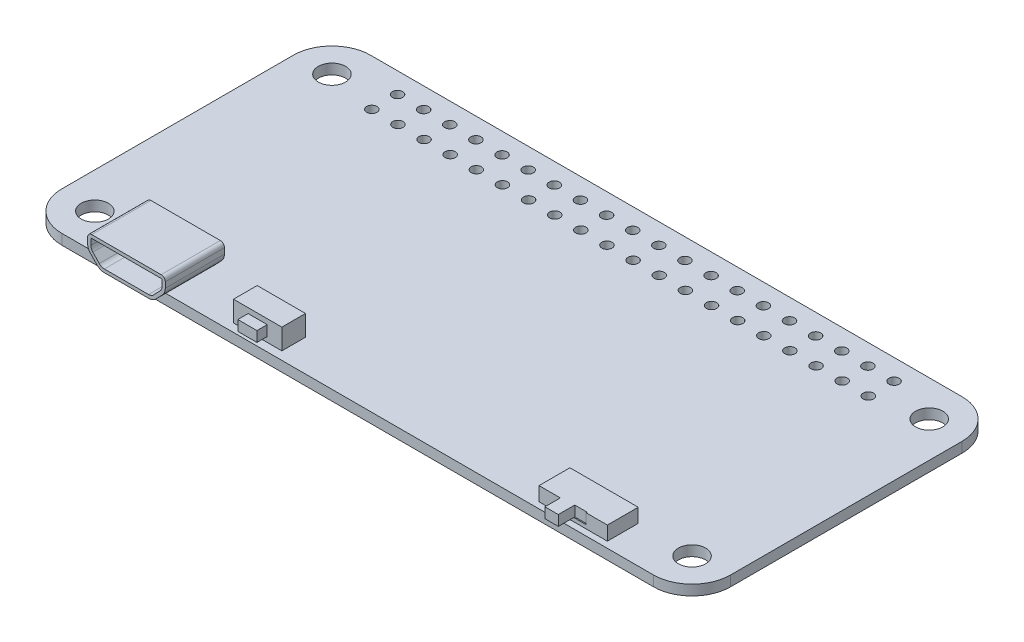
SolidWorks part; units mm, degrees
ref_plane "Front Plane" through (0, 0, 0) normal (0, 0, 1) x (1, 0, 0)
ref_plane "Top Plane" through (0, 0, 0) normal (0, 1, 0) x (1, 0, 0)
ref_plane "Right Plane" through (0, 0, 0) normal (1, 0, 0) x (0, 0, -1)
sketch "Sketch1" plane through (0, 0, 0) normal (0, 1, 0) x (1, 0, 0)
  line L1 (-28.75, 15) -> (28.75, 15)
  line L2 (-32.5, 11.25) -> (-32.5, -11.25)
  line L3 (-28.75, -15) -> (28.75, -15)
  line L4 (32.5, 11.25) -> (32.5, -11.25)
  line L5 (-32.5, 15) -> (32.5, -15) construction
  line L6 (-32.5, -15) -> (32.5, 15) construction
  arc A0 (-32.5, -11.25) -> (-28.75, -15) centre (-28.75, -11.25) ccw
  arc A1 (28.75, -15) -> (32.5, -11.25) centre (28.75, -11.25) ccw
  arc A2 (28.75, 15) -> (32.5, 11.25) centre (28.75, 11.25) cw
  arc A3 (-28.75, 15) -> (-32.5, 11.25) centre (-28.75, 11.25) ccw
  point P0 (0, 0)
  dimension "D3" = 3.75
  dimension "D1" = 65
  dimension "D2" = 30
extrude "Boss-Extrude1" add sketch "Sketch1" along normal blind 1 contours L1 A2 L4 A1 L3 A0 L2 A3
sketch "Sketch2" plane through (0, 1, 0) normal (0, 1, 0) x (1, 0, 0)
  line L0 (0, 15) -> (0, -15) construction
  line L1 (-28.75, 15) -> (28.75, 15) construction
  line L2 (-28.75, -15) -> (28.75, -15) construction
  line L3 (-32.5, 0) -> (32.5, 0) construction
  line L4 (-32.5, 11.25) -> (-32.5, -11.25) construction
  line L5 (32.5, 11.25) -> (32.5, -11.25) construction
  circle A0 centre (-29.025, 11.525) radius 1.325
  circle A2 centre (29.025, 11.525) radius 1.325
  circle A3 centre (29.025, -11.525) radius 1.325
  circle A4 centre (-29.025, -11.525) radius 1.325
  dimension "D1" = 2.65
  dimension "D2" = 2.15
  dimension "D3" = 2.15
extrude "Cut-Extrude1" cut sketch "Sketch2" against normal through all
sketch "Sketch3" plane through (0, 1, 0) normal (0, 1, 0) x (1, 0, 0)
  line L0 (-24.128, 13) -> (-24.128, 10.5) construction
  line L3 (-28.75, 15) -> (28.75, 15) construction
  line L5 (-32.5, 11.25) -> (-32.5, -11.25) construction
  circle A0 centre (-24.128, 13) radius 0.5
  circle A1 centre (-24.128, 10.5) radius 0.5
  dimension "D1" = 1
  dimension "D3" = 1.5
  dimension "D4" = 7.872
  dimension "D2" = 2.5
extrude "Cut-Extrude2" cut sketch "Sketch3" against normal through all
pattern_linear "LPattern1" count 20 spacing 2.54 along (1, 0, 0) of "Cut-Extrude2"
sketch "Sketch15" plane through (0, 0, 15) normal (0, 0, 1) x (1, 0, 0)
  line L0 (-21.225, 1) -> (-21.225, 3.6) construction
  line L1 (-28.75, 1) -> (28.75, 1) construction
  line L2 (-24.6, 3.6) -> (-17.85, 3.6)
  line L3 (-17.45, 3.2) -> (-17.45, 2.6523)
  line L4 (-17.7286, 1.9598) -> (-18.3548, 1.3075)
  line L5 (-19.0762, 1) -> (-23.3738, 1)
  line L7 (-24.7214, 1.9598) -> (-24.0952, 1.3075)
  line L8 (-25, 3.2) -> (-25, 2.6523)
  line L9 (15.325, 0) -> (15.325, 5.5788) construction
  line L10 (-28.75, 0) -> (28.75, 0) construction
  line L11 (-32.5, 1) -> (-32.5, 0) construction
  arc A0 (-18.3548, 1.3075) -> (-19.0762, 1) centre (-19.0762, 2) cw
  arc A1 (-24.0952, 1.3075) -> (-23.3738, 1) centre (-23.3738, 2) ccw
  arc A2 (-17.45, 2.6523) -> (-17.7286, 1.9598) centre (-18.45, 2.6523) cw
  arc A3 (-24.7214, 1.9598) -> (-25, 2.6523) centre (-24, 2.6523) cw
  arc A4 (-17.85, 3.6) -> (-17.45, 3.2) centre (-17.85, 3.2) cw
  arc A5 (-25, 3.2) -> (-24.6, 3.6) centre (-24.6, 3.2) cw
  point P14 (-18.65, 1)
  point P17 (-23.8, 1)
  point P20 (-17.45, 2.25)
  point P23 (-25, 2.25)
  point P26 (-17.45, 3.6)
  point P29 (-25, 3.6)
  dimension "D6" = 1
  dimension "D7" = 0.4
  dimension "D1" = 7.55
  dimension "D2" = 2.6
  dimension "D3" = 1.35
  dimension "D4" = 5.15
  dimension "D5" = 7.5
extrude "Boss-Extrude6" add sketch "Sketch15" along normal blind 1.25 and the other way blind 4.5
sketch "Sketch16" plane through (0, 0, 16.25) normal (0, 0, 1) x (1, 0, 0)
  line L30 (-18.5857, 1.5291) -> (-17.9595, 2.1814)
  line L31 (-17.77, 2.6523) -> (-17.77, 3.2)
  line L32 (-17.85, 3.28) -> (-24.6, 3.28)
  line L33 (-24.68, 3.2) -> (-24.68, 2.6523)
  line L34 (-24.4905, 2.1814) -> (-23.8643, 1.5291)
  line L35 (-23.3738, 1.32) -> (-19.0762, 1.32)
  line L36 (-18.5857, 1.5291) -> (-17.9595, 2.1814)
  line L37 (-17.77, 2.6523) -> (-17.77, 3.2)
  line L38 (-17.85, 3.28) -> (-24.6, 3.28)
  line L39 (-24.68, 3.2) -> (-24.68, 2.6523)
  line L40 (-24.4905, 2.1814) -> (-23.8643, 1.5291)
  line L41 (-23.3738, 1.32) -> (-19.0762, 1.32)
  arc A30 (-19.0762, 1.32) -> (-18.5857, 1.5291) centre (-19.0762, 2) ccw
  arc A31 (-17.9595, 2.1814) -> (-17.77, 2.6523) centre (-18.45, 2.6523) ccw
  arc A32 (-17.77, 3.2) -> (-17.85, 3.28) centre (-17.85, 3.2) ccw
  arc A33 (-24.6, 3.28) -> (-24.68, 3.2) centre (-24.6, 3.2) ccw
  arc A34 (-24.68, 2.6523) -> (-24.4905, 2.1814) centre (-24, 2.6523) ccw
  arc A35 (-23.8643, 1.5291) -> (-23.3738, 1.32) centre (-23.3738, 2) ccw
  arc A36 (-19.0762, 1.32) -> (-18.5857, 1.5291) centre (-19.0762, 2) ccw
  arc A37 (-17.9595, 2.1814) -> (-17.77, 2.6523) centre (-18.45, 2.6523) ccw
  arc A38 (-17.77, 3.2) -> (-17.85, 3.28) centre (-17.85, 3.2) ccw
  arc A39 (-24.6, 3.28) -> (-24.68, 3.2) centre (-24.6, 3.2) ccw
  arc A40 (-24.68, 2.6523) -> (-24.4905, 2.1814) centre (-24, 2.6523) ccw
  arc A41 (-23.8643, 1.5291) -> (-23.3738, 1.32) centre (-23.3738, 2) ccw
  dimension "D2" = 0.32
extrude "Cut-Extrude9" cut sketch "Sketch16" against normal blind 5.25
sketch "草图1" plane through (0, 1, 0) normal (0, 1, 0) x (1, 0, 0)
  line L0 (-32.5, 11.25) -> (-32.5, -11.25) construction
  line L1 (-12.87, -11.9) -> (-8.17, -11.9)
  line L2 (-12.87, -11.9) -> (-12.87, -14.2)
  line L3 (-12.87, -14.2) -> (-8.17, -14.2)
  line L4 (-8.17, -11.9) -> (-8.17, -14.2)
  line L5 (-28.75, -15) -> (-23.3738, -15) construction
  dimension "D1" = 4.7
  dimension "D2" = 2.3
  dimension "D3" = 19.63
  dimension "D4" = 0.8
extrude "凸台-拉伸1" add sketch "草图1" along normal blind 2
sketch "草图2" plane through (0, 0, 14.2) normal (0, 0, 1) x (1, 0, 0)
  line L0 (-12.87, 3) -> (-8.17, 3) construction
  line L5 (-11.45, 2.5) -> (-9.59, 2.5)
  line L6 (-11.45, 2.5) -> (-11.45, 1.5)
  line L7 (-11.45, 1.5) -> (-9.59, 1.5)
  line L8 (-9.59, 2.5) -> (-9.59, 1.5)
  line L9 (-11.45, 2.5) -> (-9.59, 1.5) construction
  line L10 (-11.45, 1.5) -> (-9.59, 2.5) construction
  line L11 (-8.17, 3) -> (-8.17, 1) construction
  point P0 (-10.52, 2)
  point P8 (-10.52, 3)
  point P12 (-8.17, 2)
  dimension "D1" = 1.86
  dimension "D2" = 1
extrude "凸台-拉伸2" add sketch "草图2" along normal blind 1
sketch "草图3" plane through (0, 0, 0) normal (0, -1, 0) x (1, 0, 0)
  line L0 (-32.5, -11.25) -> (-32.5, 11.25) construction
  line L1 (-30.9, -7) -> (-28.4, -7)
  line L2 (-30.9, -7) -> (-30.9, -5.75)
  line L3 (-30.9, -5.75) -> (-28.4, -5.75)
  line L4 (-28.4, -7) -> (-28.4, -5.75)
  line L5 (-30.9, -3.15) -> (-28.4, -3.15)
  line L6 (-30.9, -3.15) -> (-30.9, -1.9)
  line L7 (-30.9, -1.9) -> (-28.4, -1.9)
  line L8 (-28.4, -3.15) -> (-28.4, -1.9)
  line L9 (-30.9, 0.7) -> (-28.4, 0.7)
  line L10 (-30.9, 0.7) -> (-30.9, 1.95)
  line L11 (-30.9, 1.95) -> (-28.4, 1.95)
  line L12 (-28.4, 0.7) -> (-28.4, 1.95)
  line L13 (-30.9, 4.55) -> (-28.4, 4.55)
  line L14 (-30.9, 4.55) -> (-30.9, 5.8)
  line L15 (-30.9, 5.8) -> (-28.4, 5.8)
  line L16 (-28.4, 4.55) -> (-28.4, 5.8)
  line L17 (-28.75, -15) -> (28.75, -15) construction
  dimension "D1" = 1.25
  dimension "D2" = 2.5
  dimension "D3" = 2.6
  dimension "D4" = 2.6
  dimension "D5" = 2.6
  dimension "D6" = 1.6
  dimension "D7" = 8
extrude "凸台-拉伸3" add sketch "草图3" along normal blind 0.8
sketch "草图4" plane through (0, 0, 0) normal (0, -1, 0) x (1, 0, 0)
  line L0 (-28.75, 15) -> (28.75, 15) construction
  line L1 (-22.64, 10.68) -> (-19.34, 10.68)
  line L2 (-22.64, 10.68) -> (-22.64, 11.68)
  line L3 (-22.64, 11.68) -> (-19.34, 11.68)
  line L4 (-19.34, 10.68) -> (-19.34, 11.68)
  line L5 (-22.64, 8.38) -> (-19.2262, 8.38)
  line L6 (-22.64, 8.38) -> (-22.64, 9.38)
  line L7 (-22.64, 9.38) -> (-19.2262, 9.38)
  line L8 (-19.2262, 8.38) -> (-19.2262, 9.38)
  line L9 (-32.5, -11.25) -> (-32.5, 11.25) construction
  dimension "D1" = 3.3
  dimension "D2" = 1
  dimension "D3" = 1.3
  dimension "D4" = 3.32
  dimension "D5" = 9.86
extrude "凸台-拉伸4" add sketch "草图4" along normal blind 0.6
sketch "草图5" plane through (0, -0.6, 0) normal (0, -1, 0) x (1, 0, 0)
  line L0 (-19.2262, 9.38) -> (-22.64, 9.38) construction
  line L1 (-22.64, 8.38) -> (-21.44, 8.38)
  line L2 (-22.64, 8.38) -> (-22.64, 9.38)
  line L3 (-22.64, 9.38) -> (-21.44, 9.38)
  line L4 (-21.44, 8.38) -> (-21.44, 9.38)
  line L5 (-19.34, 11.68) -> (-22.64, 11.68) construction
  line L6 (-22.64, 10.68) -> (-21.44, 10.68)
  line L7 (-22.64, 10.68) -> (-22.64, 11.68)
  line L8 (-22.64, 11.68) -> (-21.44, 11.68)
  line L9 (-21.44, 10.68) -> (-21.44, 11.68)
  dimension "D1" = 1.2
extrude "凸台-拉伸5" add sketch "草图5" along normal blind 0.9 draft 22
sketch "草图6" plane through (0, 1, 0) normal (0, 1, 0) x (1, 0, 0)
  line L0 (32.5, 11.25) -> (32.5, -11.25) construction
  line L1 (23.67, -11.4) -> (17.03, -11.4)
  line L2 (23.67, -11.4) -> (23.67, -14.4)
  line L3 (23.67, -14.4) -> (17.03, -14.4)
  line L4 (17.03, -11.4) -> (17.03, -14.4)
  line L5 (23.67, -11.4) -> (17.03, -14.4) construction
  line L6 (23.67, -14.4) -> (17.03, -11.4) construction
  line L7 (-19.0762, -15) -> (28.75, -15) construction
  point P0 (20.35, -12.9)
  dimension "D1" = 8.83
  dimension "D2" = 6.64
  dimension "D3" = 3
  dimension "D4" = 0.6
extrude "凸台-拉伸6" add sketch "草图6" along normal blind 1.36
sketch "草图7" plane through (0, 0, 14.4) normal (0, 0, 1) x (1, 0, 0)
  line L0 (17.03, 2.36) -> (23.67, 2.36) construction
  line L1 (19.1, 2.36) -> (21.6, 2.36)
  line L2 (19.1, 2.36) -> (19.1, 1.36)
  line L3 (19.1, 1.36) -> (21.6, 1.36)
  line L4 (21.6, 2.36) -> (21.6, 1.36)
  line L5 (23.67, 2.36) -> (17.03, 2.36) construction
  point P8 (20.35, 2.36)
  point P9 (20.35, 2.36)
  dimension "D1" = 1
  dimension "D2" = 2.5
extrude "切除-拉伸1" cut sketch "草图7" against normal blind 0.1
sketch "草图8" plane through (0, 0, 14.3) normal (0, 0, 1) x (1, 0, 0)
  line L0 (19.1, 2.36) -> (19.1, 1.36) construction
  line L1 (19.1, 2.36) -> (20.4, 2.36)
  line L2 (19.1, 2.36) -> (19.1, 1.36)
  line L3 (19.1, 1.36) -> (20.4, 1.36)
  line L4 (20.4, 2.36) -> (20.4, 1.36)
  line L5 (21.6, 2.36) -> (19.1, 2.36) construction
  line L6 (19.1, 1.36) -> (21.6, 1.36) construction
  dimension "D1" = 1.3
extrude "凸台-拉伸7" add sketch "草图8" along normal blind 1.6
